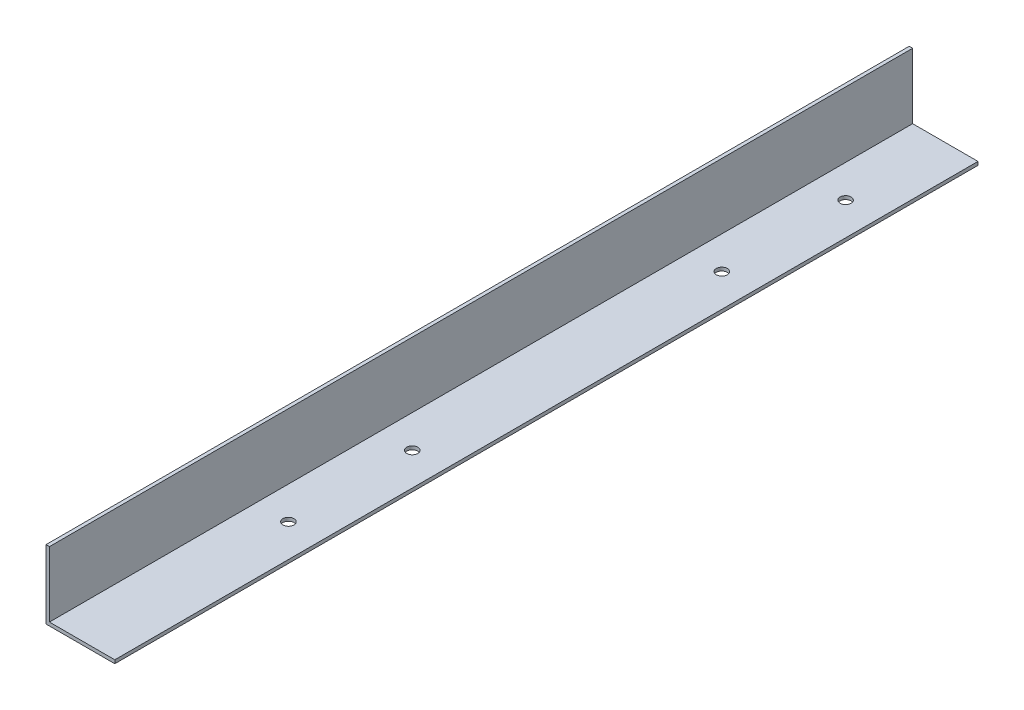
SolidWorks part; units mm, degrees
material "1060 Сплав"
ref_plane "Спереди" through (0, 0, 0) normal (0, 0, 1) x (1, 0, 0)
ref_plane "Сверху" through (0, 0, 0) normal (0, 1, 0) x (1, 0, 0)
ref_plane "Справа" through (0, 0, 0) normal (1, 0, 0) x (0, 0, -1)
sketch "Эскиз1" plane through (0, 0, 0) normal (0, 0, 1) x (1, 0, 0)
  line L0 (0, 0) -> (0, 20)
  line L1 (0, 20) -> (1, 20)
  line L2 (1, 20) -> (1, 1)
  line L3 (1, 1) -> (20, 1)
  line L4 (20, 1) -> (20, 0)
  line L5 (20, 0) -> (0, 0)
  dimension "D1" = 20
  dimension "D2" = 1
extrude "Бобышка-Вытянуть1" add sketch "Эскиз1" along normal blind 251
sketch "Эскиз2" plane through (0, 1, 0) normal (0, 1, 0) x (1, 0, 0)
  line L0 (10.5, 0) -> (10.5, -251) construction
  line L1 (20, 0) -> (1, 0) construction
  line L2 (20, -251) -> (1, -251) construction
ref_plane "Плоскость1" through (10.5, 0, 0) normal (-1, 0, 0) x (0, 0, 1)
sketch "Эскиз3" plane through (0, 1, 0) normal (0, 1, 0) x (1, 0, 0)
  line L0 (10.5, 0) -> (10.5, -251) construction
  line L1 (20, 0) -> (1, 0) construction
  line L2 (20, -251) -> (1, -251) construction
  circle A1 centre (10.5, -29) radius 1.6
  circle A3 centre (10.5, -65) radius 1.6
  circle A5 centre (10.5, -155) radius 1.6
  circle A7 centre (10.5, -191) radius 1.6
  dimension "D1" = 3.2
  dimension "D2" = 29
  dimension "D3" = 65
  dimension "D4" = 60
  dimension "D5" = 96
extrude "Вырез-Вытянуть1" cut sketch "Эскиз3" against normal through all
